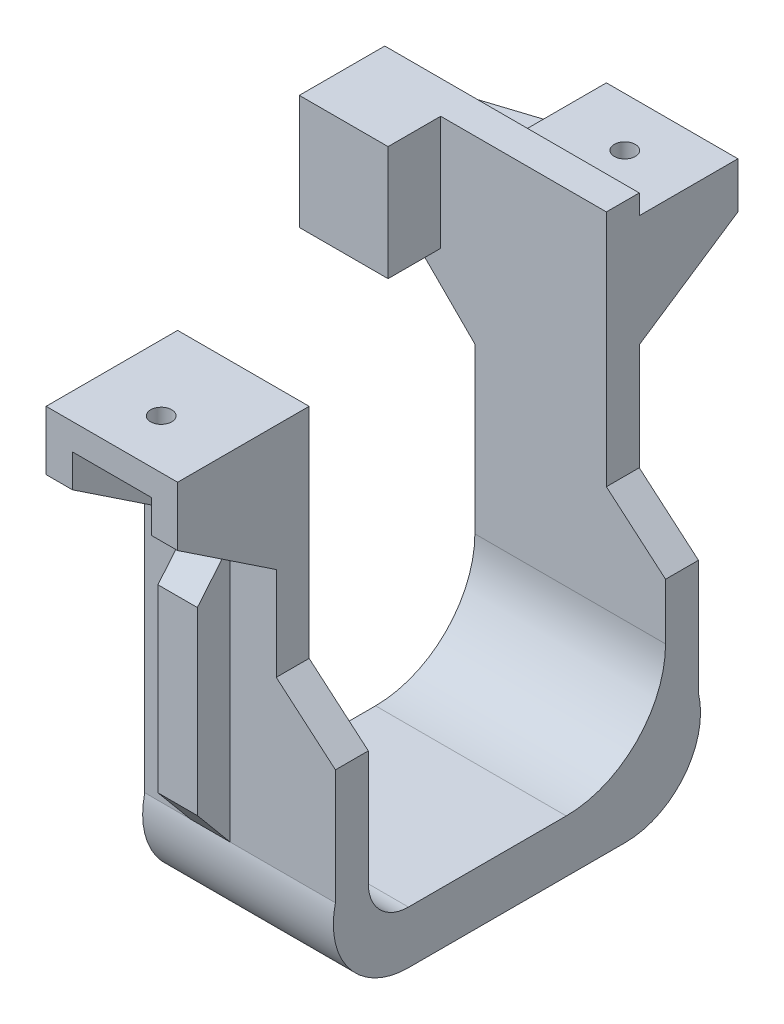
SolidWorks part; units mm, degrees
ref_plane "Plano frontal" through (0, 0, 0) normal (0, 0, 1) x (1, 0, 0)
ref_plane "Plano superior" through (0, 0, 0) normal (0, 1, 0) x (1, 0, 0)
ref_plane "Plano direito" through (0, 0, 0) normal (1, 0, 0) x (0, 0, -1)
sketch "Esboço1" plane through (0, 0, 0) normal (0, 0, 1) x (1, 0, 0)
  line L0 (0, 0) -> (0, 58.4)
  line L5 (0, 58.4) -> (20, 58.4)
  line L6 (20, 58.4) -> (20, 25.2)
  line L7 (20, 25.2) -> (29, 17.52)
  line L8 (29, 17.52) -> (29, 0)
  line L9 (29, 0) -> (0, 0)
  dimension "D1" = 58.4
  dimension "D2" = 20
  dimension "D3" = 29
  dimension "D4" = 17.52
  dimension "D5" = 33.2
extrude "Ressalto-extrusão1" add sketch "Esboço1" along normal blind 5
sketch "Esboço2" plane through (0, 0, 0) normal (-1, 0, 0) x (0, 0, 1)
  line L0 (0, 0) -> (5, 0)
  line L1 (-6.1023, -6.1) -> (-6.1019, -14.1) construction
  line L2 (-6.1023, -6.1) -> (-30.1023, -6.1)
  line L4 (-39.1023, -14.1) -> (-6.1019, -14.1)
  line L5 (-50.2046, 0.0023) -> (-50.2046, 61.4)
  line L6 (-50.2046, 61.4) -> (-45.2046, 61.4)
  line L7 (-45.2046, 61.4) -> (-45.2046, 9.0023)
  arc A0 (-6.1023, -6.1) -> (0, 0) centre (-6.1023, 0.0023) ccw
  arc A1 (-6.1019, -14.1) -> (5, 0) centre (-6.1019, -2.6793) ccw
  arc A2 (-45.2046, 9.0023) -> (-30.1023, -6.1) centre (-30.1023, 9.0023) ccw
  arc A3 (-50.2046, 0.0023) -> (-39.1023, -14.1) centre (-39.1023, -2.6786) ccw
extrude "Ressalto-extrusão2" add sketch "Esboço2" against normal blind 29
sketch "Esboço3" plane through (0, 0, -50.2046) normal (0, 0, -1) x (-1, 0, 0)
  line L0 (-29, 17.52) -> (-20, 25.2011)
  line L1 (-20, 25.2011) -> (-20, 61.4)
  line L2 (-29, 61.4) -> (0, 61.4) construction
  line L3 (-20, 61.4) -> (-20, 58.4) construction
  line L4 (-20, 61.4) -> (-29, 61.4)
  line L5 (-29, 61.4) -> (-29, 17.52)
extrude "Corte-extrusão1" cut sketch "Esboço3" against normal up to next
sketch "Esboço4" plane through (0, 0, -50.2046) normal (0, 0, -1) x (-1, 0, 0)
  line L0 (0, 34.0023) -> (10, 44.0023)
  line L1 (0, 61.4) -> (0, 0.0023) construction
  line L2 (0, 34.0023) -> (10, 44.0023) construction
  line L3 (10, 44.0023) -> (18.7, 44.0023)
  line L4 (0, 49.7011) -> (18.7, 44.0023) construction
  line L5 (10, 44.0023) -> (18.7, 44.0023) construction
  line L6 (18.7, 44.0023) -> (18.7, 61.4)
  line L7 (18.7, 61.4) -> (0, 61.4)
  line L8 (0, 61.4) -> (0, 34.0023)
extrude "Ressalto-extrusão3" add sketch "Esboço4" against normal blind 5
sketch "Esboço5" plane through (0, 0, -45.2046) normal (0, 0, 1) x (1, 0, 0)
  line L1 (-18.7, 61.4) -> (-5.2, 61.4)
  line L2 (-18.7, 61.4) -> (-18.7, 44.0023)
  line L3 (-18.7, 44.0023) -> (-5.2, 44.0023)
  line L4 (-5.2, 61.4) -> (-5.2, 44.0023)
extrude "Ressalto-extrusão4" add sketch "Esboço5" along normal blind 8
sketch "Esboço6" plane through (20, 0, 0) normal (1, 0, 0) x (0, 0, -1)
  line L0 (50.2046, 58.4) -> (65.2046, 58.4)
  line L1 (50.2046, 25.2011) -> (50.2046, 61.4) construction
  line L2 (65.2046, 58.4) -> (65.2046, 51.4)
  line L3 (65.2046, 51.4) -> (50.2046, 41.4)
  line L4 (50.2046, 41.4) -> (55.2046, 35.4) construction
  line L5 (50.2046, 41.4) -> (50.2046, 58.4)
  line L6 (50.2046, 41.4) -> (50.2046, 61.4) construction
extrude "Ressalto-extrusão5" add sketch "Esboço6" against normal blind 20
sketch "Esboço7" plane through (0, 0, -50.2046) normal (0, 0, -1) x (-1, 0, 0)
  line L0 (0, 41.4) -> (-20, 41.4) construction
  line L1 (-16, 54.4) -> (-4.5, 54.4)
  line L2 (-16, 54.4) -> (-16, 41.4)
  line L3 (-16, 41.4) -> (-4.5, 41.4)
  line L4 (-4.5, 54.4) -> (-4.5, 41.4)
  line L5 (-4.5, 51.4) -> (-4.5, 41.4) construction
extrude "Corte-extrusão2" cut sketch "Esboço7" along normal blind 20
sketch "Esboço8" plane through (20, 0, 0) normal (1, 0, 0) x (0, 0, -1)
  line L0 (-5, 58.4) -> (-20, 58.4)
  line L1 (-20, 58.4) -> (-20, 49.4)
  line L2 (-20, 49.4) -> (-5, 39.4)
  line L3 (-5, 25.2) -> (-5, 58.4) construction
  line L4 (-10, 33.4) -> (-5, 39.4) construction
  line L5 (-5, 39.4) -> (-5, 58.4)
extrude "Ressalto-extrusão6" add sketch "Esboço8" against normal blind 20
sketch "Esboço9" plane through (0, 0, 5) normal (0, 0, 1) x (1, 0, 0)
  line L0 (0, 39.4) -> (20, 39.4) construction
  line L1 (4, 54.4) -> (16, 54.4)
  line L2 (4, 54.4) -> (4, 39.4)
  line L3 (4, 39.4) -> (16, 39.4)
  line L4 (16, 54.4) -> (16, 39.4)
  dimension "D1" = 12
extrude "Corte-extrusão3" cut sketch "Esboço9" along normal blind 20
sketch "Esboço11" plane through (0, 0, 5) normal (0, 0, 1) x (1, 0, 0)
  line L0 (13, 6.0023) -> (13, 0.0023) construction
  line L1 (7, 39.4) -> (13, 39.4)
  line L2 (7, 39.4) -> (7, 0)
  line L3 (7, 0) -> (13, 0)
  line L4 (13, 39.4) -> (13, 0)
  line L5 (13, 6.0023) -> (13, 0.0023) construction
  line L6 (0, 0) -> (29, 0) construction
extrude "Ressalto-extrusão7" add sketch "Esboço11" along normal blind 5
sketch "Esboço12" plane through (0, 0, -50.2046) normal (0, 0, -1) x (-1, 0, 0)
  line L0 (-29, 0.0023) -> (0, 0.0023) construction
  line L1 (-13.25, 41.4) -> (-7.25, 41.4)
  line L2 (-13.25, 41.4) -> (-13.25, 0.0023)
  line L3 (-13.25, 0.0023) -> (-7.25, 0.0023)
  line L4 (-7.25, 41.4) -> (-7.25, 0.0023)
  line L5 (-7.25, 0.0023) -> (0, -1.6943) construction
extrude "Ressalto-extrusão8" add sketch "Esboço12" along normal blind 5
chamfer "Chanfro1" distance 5 distance2 6 4 edges at (10, 0, 10) (10, 39.4, 10) (10.25, 0.0023, -55.2046) (10.25, 41.4, -55.2046) first distance on face at (10, 0, 7.5) first distance on face at (10, 39.4, 7.5) first distance on face at (10.25, 0.0023, -52.7046) first distance on face at (10.25, 41.4, -52.7046)
sketch "Esboço13" plane through (0, 61.4, 0) normal (0, 1, 0) x (1, 0, 0)
  line L0 (-18.7, 50.2046) -> (-18.7, 53.2046)
  line L1 (-18.7, 53.2046) -> (0, 59.2046)
  line L2 (0, 65.2046) -> (0, 50.2046) construction
  line L3 (0, 59.2046) -> (0, 50.2046)
  line L4 (0, 50.2046) -> (-18.7, 50.2046)
  dimension "D1" = 9
extrude "Ressalto-extrusão9" add sketch "Esboço13" against normal blind 6 from offset 5.7 offset against normal yes
sketch "Esboço14" plane through (0, 58.4, 0) normal (0, 1, 0) x (1, 0, 0)
  line L0 (20, 65.2046) -> (20, 50.2046) construction
  line L1 (0, 65.2046) -> (0, 50.2046) construction
  line L2 (0, -20) -> (20, -20) construction
  circle A0 centre (10.3, 57.7046) radius 1.6
  circle A1 centre (10, -12.5) radius 1.6
  point P5 (20, 57.7046)
  point P12 (10, -20)
  dimension "D1" = 3.2
  dimension "D3" = 3.2
  dimension "D2" = 10.3
  dimension "D4" = 7.5
extrude "Corte-extrusão4" cut sketch "Esboço14" against normal blind 6
